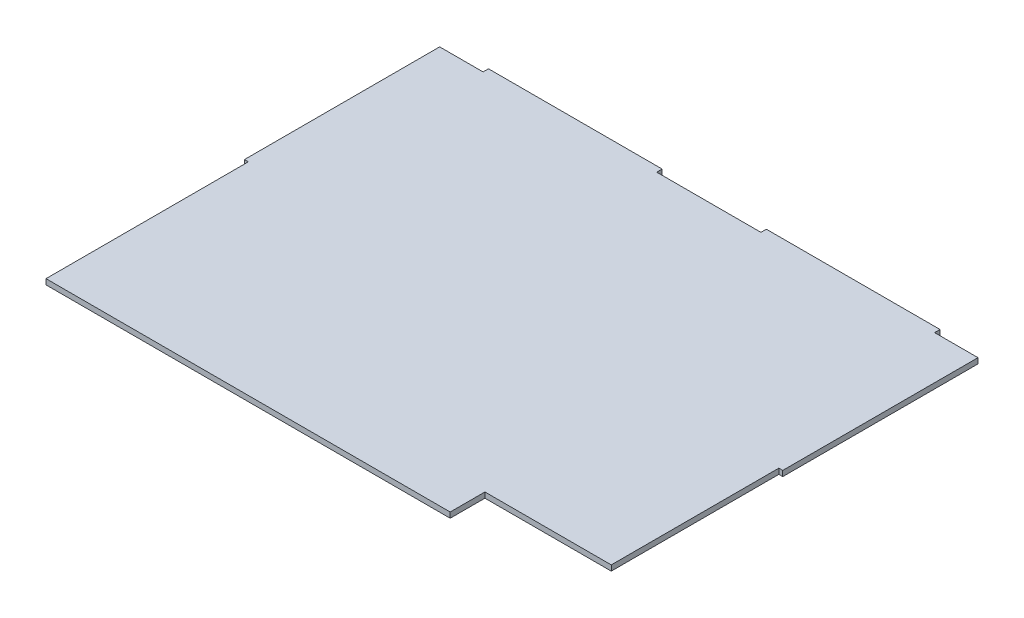
SolidWorks part; units mm, degrees
material "6061-T6 (SS)"
ref_plane "X-Y Datum" through (0, 0, 0) normal (0, 0, 1) x (1, 0, 0)
ref_plane "X-Z Datum" through (0, 0, 0) normal (0, 1, 0) x (1, 0, 0)
ref_plane "Y-Z Datum" through (0, 0, 0) normal (1, 0, 0) x (0, 0, -1)
sketch "Sketch1" plane through (0, 0, 0) normal (0, 0, 1) x (1, 0, 0)
  line L1 (-157.4823, -1.5875) -> (157.4823, -1.5875)
  line L2 (-157.4823, -1.5875) -> (-157.4823, 1.5875)
  line L3 (-157.4823, 1.5875) -> (157.4823, 1.5875)
  line L4 (157.4823, -1.5875) -> (157.4823, 1.5875)
  line L5 (-157.4823, -1.5875) -> (157.4823, 1.5875) construction
  line L6 (-157.4823, 1.5875) -> (157.4823, -1.5875) construction
  point P0 (0, 0)
  dimension "D1" = 314.9646
  dimension "D2" = 3.175
extrude "Boss-Extrude1" add sketch "Sketch1" along normal blind 235.775
sketch "Sketch3" plane through (0, 0, 0) normal (0, 0, -1) x (-1, 0, 0)
  line L0 (-157.4823, 0) -> (-81.2823, 0) construction
  line L1 (-157.4823, -1.5875) -> (-157.4823, 1.5875) construction
  line L2 (-157.4823, 1.5875) -> (157.4823, 1.5875) construction
  line L3 (-132.0823, -1.5875) -> (-30.4823, -1.5875)
  line L4 (-132.0823, -1.5875) -> (-132.0823, 1.5875)
  line L5 (-132.0823, 1.5875) -> (-30.4823, 1.5875)
  line L6 (-30.4823, -1.5875) -> (-30.4823, 1.5875)
  line L7 (-132.0823, -1.5875) -> (-30.4823, 1.5875) construction
  line L8 (-132.0823, 1.5875) -> (-30.4823, -1.5875) construction
  line L14 (-157.4823, 1.5875) -> (-132.0823, 1.5875)
  line L15 (-157.4823, 1.5875) -> (-157.4823, -1.5875)
  line L16 (-157.4823, -1.5875) -> (-132.0823, -1.5875)
  line L17 (-132.0823, 1.5875) -> (-132.0823, -1.5875)
  line L19 (-30.4823, 1.5875) -> (-30.4823, -1.5875)
  line L20 (0, 43.0151) -> (0, -43.0151) construction
  line L21 (30.4823, -1.5875) -> (30.4823, 1.5875)
  line L22 (132.0823, -1.5875) -> (132.0823, 1.5875)
  line L23 (132.0823, 1.5875) -> (30.4823, 1.5875)
  line L24 (132.0823, -1.5875) -> (30.4823, 1.5875) construction
  line L25 (132.0823, -1.5875) -> (30.4823, -1.5875)
  line L26 (132.0823, 1.5875) -> (30.4823, -1.5875) construction
  line M2 (-157.4823, 1.5875) -> (-157.4823, -1.5875)
  line M3 (-157.4823, -1.5875) -> (157.4823, -1.5875)
  line M4 (157.4823, -1.5875) -> (157.4823, 1.5875)
  line M5 (157.4823, 1.5875) -> (-157.4823, 1.5875)
  dimension "D1" = 76.2
  dimension "D2" = 101.6
extrude "Cut-Extrude1" cut sketch "Sketch3" against normal blind 3.175 contours L4 M3 M5 M2 | L6 M3 M5 | M3 M4 M5 region at (144.7823, 0, 0) region at (0, 0, 0) region at (-144.7823, 0, 0)
sketch "Sketch5" plane through (0, 1.5875, 0) normal (0, 1, 0) x (1, 0, 0)
  line L1 (-157.4823, -235.775) -> (-155.1963, -235.775)
  line L3 (-157.4823, -235.775) -> (-157.4823, -117.411)
  line L5 (-157.4823, -117.411) -> (-155.1963, -117.411)
  line L6 (-155.1963, -235.775) -> (-155.1963, -117.411)
  line M11 (-157.4823, -3.175) -> (-157.4823, -235.775)
  line M12 (-157.4823, -235.775) -> (157.4823, -235.775)
  dimension "D1" = 118.364
  dimension "D2" = 2.286
extrude "Cut-Extrude2" cut sketch "Sketch5" against normal blind 3.175 and the other way through all contours M12 M11 region at (-156.3393, 1.5875, 176.593)
mirror "Mirror1" about plane through (0, 0, 0) normal (1, 0, 0) of "Cut-Extrude2"
sketch "Sketch6" plane through (0, 1.5875, 0) normal (0, 1, 0) x (1, 0, 0)
  line L6 (-157.4823, -215.455) -> (-81.2823, -215.455)
  line L7 (-157.4823, -215.455) -> (-157.4823, -235.775)
  line L8 (-157.4823, -235.775) -> (-81.2823, -235.775)
  line L9 (-81.2823, -215.455) -> (-81.2823, -235.775)
  line L10 (155.1963, -235.775) -> (-155.1963, -235.775) construction
  line L11 (-157.4823, -117.411) -> (-157.4823, -3.175) construction
  line L13 (155.1963, -235.775) -> (-81.2823, -235.775)
  line L14 (155.1963, -235.775) -> (155.1963, -215.455)
  line L15 (155.1963, -215.455) -> (-81.2823, -215.455)
  line L16 (-81.2823, -235.775) -> (-81.2823, -215.455)
  line M18 (-155.1963, -117.411) -> (-155.1963, -235.775)
  line M19 (-155.1963, -235.775) -> (155.1963, -235.775)
  dimension "D1" = 76.2
  dimension "D2" = 20.32
extrude "Cut-Extrude4" [suppressed] cut sketch "Sketch6" against normal through all contours L9 L6 M18 M19
sketch "Sketch7" [suppressed] plane through (0, 1.5875, 0) normal (0, 1, 0) x (1, 0, 0)
  line L1 (-81.2823, -215.455) -> (155.1963, -215.455)
  line L2 (-81.2823, -215.455) -> (-81.2823, -235.775)
  line L3 (-81.2823, -235.775) -> (155.1963, -235.775)
  line L4 (155.1963, -215.455) -> (155.1963, -235.775)
extrude "Cut-Extrude5" [suppressed] cut sketch "Sketch7" against normal through all
sketch "Sketch8" plane through (0, 1.5875, 0) normal (0, 1, 0) x (1, 0, 0)
  line L0 (155.1963, -235.775) -> (-155.1963, -235.775) construction
  line L1 (157.4823, -215.455) -> (81.2823, -215.455)
  line L2 (157.4823, -215.455) -> (157.4823, -235.775)
  line L3 (157.4823, -235.775) -> (81.2823, -235.775)
  line L4 (81.2823, -215.455) -> (81.2823, -235.775)
  line L5 (157.4823, -117.411) -> (157.4823, -3.175) construction
  dimension "D1" = 20.32
  dimension "D2" = 76.2
extrude "Cut-Extrude6" cut sketch "Sketch8" against normal through all
sketch "Sketch9" [suppressed] plane through (0, 0, 215.455) normal (0, 0, 1) x (1, 0, 0)
  line L4 (155.1963, 1.5875) -> (-155.1963, 1.5875)
  line L5 (-155.1963, 1.5875) -> (-155.1963, -1.5875)
  line L6 (-155.1963, -1.5875) -> (155.1963, -1.5875)
  line L7 (155.1963, -1.5875) -> (155.1963, 1.5875)
  line L8 (155.1963, 1.5875) -> (-155.1963, 1.5875)
  line L9 (-155.1963, 1.5875) -> (-155.1963, -1.5875)
  line L10 (-155.1963, -1.5875) -> (155.1963, -1.5875)
  line L11 (155.1963, -1.5875) -> (155.1963, 1.5875)
  dimension "D1" = 0
extrude "Cut-Extrude7" [suppressed] cut sketch "Sketch9" against normal blind 11.68
